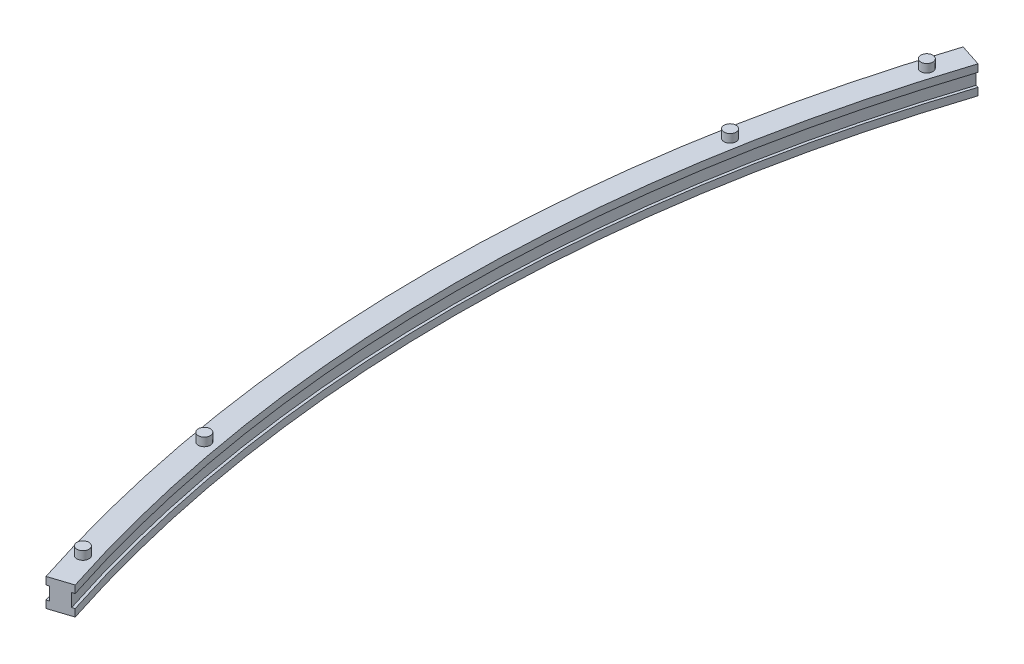
SolidWorks part; units mm, degrees
ref_plane "Front Plane" through (0, 0, 0) normal (0, 0, 1) x (1, 0, 0)
ref_plane "Top Plane" through (0, 0, 0) normal (0, 1, 0) x (1, 0, 0)
ref_plane "Right Plane" through (0, 0, 0) normal (1, 0, 0) x (0, 0, -1)
sketch "Sketch1" plane through (0, 0, 0) normal (0, 1, 0) x (1, 0, 0)
  line L0 (-152.239, 45.522) -> (-152.239, -45.522) construction
  line L1 (-156.303, 28.364) -> (-156.303, -28.364) construction
  line L2 (-157.5329, -28.5872) -> (-155.0731, -28.1408) construction
  line L3 (-153.3949, -45.8676) -> (-150.9997, -45.1514) construction
  line L4 (-149.892, -48.7029) -> (-152.2696, -49.4754)
  line L5 (-149.892, 48.7029) -> (-152.2696, 49.4754)
  arc A0 (-152.2696, 49.4754) -> (-152.2696, -49.4754) centre (0, 0) ccw
  arc A1 (-149.892, 48.7029) -> (-149.892, -48.7029) centre (0, 0) ccw
  circle A2 centre (-156.303, -28.364) radius 0.65
  circle A3 centre (-156.303, 28.364) radius 0.65
  circle A4 centre (-152.239, 45.522) radius 0.65
  circle A5 centre (-152.239, -45.522) radius 0.65
  point P0 (-152.239, 45.522)
  point P1 (-156.303, 28.364)
  point P4 (-152.239, -45.522)
  point P5 (-152.239, 0)
  point P6 (-156.303, -28.364)
  point P7 (-156.303, 0)
  dimension "D7" = 1.3
  dimension "D1" = 45.522
  dimension "D2" = 28.364
  dimension "D3" = 156.303
  dimension "D4" = 152.239
  dimension "D5" = 2.5
  dimension "D6" = 36
extrude "Boss-Extrude1" add sketch "Sketch1" along normal blind 0.8 contours A2 | A1 L5 A0 L4 A2 | A5 | A3 | A4 region at (-151.3882, 0, 48.143) region at (-156.303, 0, 28.364) region at (-156.303, 0, -28.364) region at (-152.239, 0, -45.522) region at (-152.239, 0, 45.522)
sketch "Sketch2" plane through (0, 0.8, 0) normal (0, 1, 0) x (1, 0, 0)
  line L0 (-149.892, -48.7029) -> (-152.2696, -49.4754) construction
  line L1 (-149.892, 48.7029) -> (-152.2696, 49.4754) construction
  line L6 (-150.1773, -48.7956) -> (-151.9843, -49.3827)
  line L7 (-150.1773, 48.7956) -> (-151.9843, 49.3827)
  arc A8 (-150.1773, 48.7956) -> (-150.1773, -48.7956) centre (0, 0) ccw
  arc A9 (-150.1773, 48.7956) -> (-150.1773, -48.7956) centre (0, 0) ccw
  arc A11 (-151.9843, 49.3827) -> (-151.9843, -49.3827) centre (0, 0) ccw
  arc A12 (-151.9843, 49.3827) -> (-151.9843, -49.3827) centre (0, 0) ccw
  dimension "D2" = 0.3
  dimension "D3" = 0.3
extrude "Boss-Extrude2" add sketch "Sketch2" along normal blind 1.4
sketch "Sketch3" plane through (0, 2.2, 0) normal (0, 1, 0) x (1, 0, 0)
  line L2 (-152.2696, -49.4754) -> (-149.892, -48.7029)
  line L3 (-149.892, 48.7029) -> (-152.2696, 49.4754)
  line L4 (-152.2696, -49.4754) -> (-149.892, -48.7029)
  line L5 (-149.892, 48.7029) -> (-152.2696, 49.4754)
  arc A2 (-149.892, 48.7029) -> (-149.892, -48.7029) centre (0, 0) ccw
  arc A3 (-152.2696, 49.4754) -> (-152.2696, -49.4754) centre (0, 0) ccw
  arc A4 (-149.892, 48.7029) -> (-149.892, -48.7029) centre (0, 0) ccw
  arc A5 (-152.2696, 49.4754) -> (-152.2696, -49.4754) centre (0, 0) ccw
  dimension "D1" = 0
extrude "Boss-Extrude3" add sketch "Sketch3" along normal blind 0.8
extrude "Boss-Extrude4" add sketch "Sketch1<3>" along normal blind 3.9 contours A2 | A4 | A5 | A3 region at (-156.303, 0, 28.364) region at (-152.239, 0, -45.522)
sketch "Sketch1<3>" plane through (0, 0, 0) normal (0, 1, 0) x (1, 0, 0) same geometry as "Sketch1"
